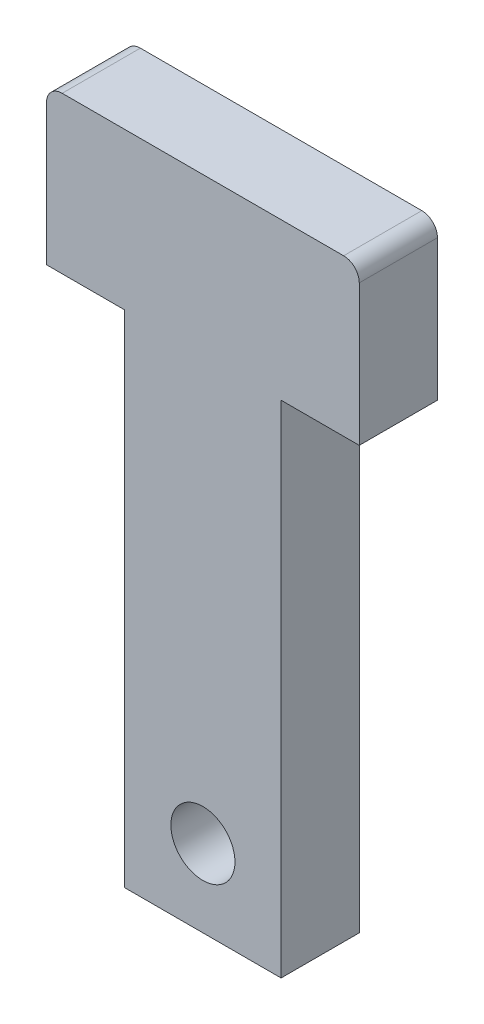
SolidWorks part; units mm, degrees
ref_plane "前基準面" through (0, 0, 0) normal (0, 0, 1) x (1, 0, 0)
ref_plane "上基準面" through (0, 0, 0) normal (0, 1, 0) x (1, 0, 0)
ref_plane "右基準面" through (0, 0, 0) normal (1, 0, 0) x (0, 0, -1)
sketch "草圖1" plane through (0, 0, 0) normal (0, 0, 1) x (1, 0, 0)
  line L0 (-5, -4.5) -> (-10, -4.5)
  line L1 (9, 5.5) -> (-9, 5.5)
  line L2 (10, 4.5) -> (10, -4.5)
  line L3 (10, -4.5) -> (5, -4.5)
  line L4 (-10, 4.5) -> (-10, -4.5)
  line L5 (0, -4.801) -> (0, 5.5) construction
  line L6 (10, 0) -> (-10, 0) construction
  line L7 (5, -36.5) -> (-5, -36.5)
  line L8 (5, -36.5) -> (5, -4.5)
  line L10 (-5, -36.5) -> (-5, -4.5)
  line L11 (0, -4.801) -> (0, -36.5) construction
  line L14 (-5, -4.5) -> (5, -4.5) construction
  line L15 (-5, -4.5) -> (-5, -9.5) construction
  line L16 (-5, -9.5) -> (5, -9.5) construction
  line L17 (5, -4.5) -> (5, -9.5) construction
  circle A0 centre (0, -31.55) radius 2.05
  arc A1 (9, 5.5) -> (10, 4.5) centre (9, 4.5) cw
  arc A2 (-9, 5.5) -> (-10, 4.5) centre (-9, 4.5) ccw
  point P0 (0, 0)
  point P4 (0, -17.2944)
  point P14 (0, -29.5)
  point P19 (10, 5.5)
  point P22 (-10, 5.5)
  dimension "D5" = 4.1
  dimension "D7" = 1
  dimension "D1" = 10
  dimension "D2" = 20
  dimension "D3" = 10
  dimension "D4" = 20
  dimension "D6" = 27
  dimension "D8" = 5
extrude "填料-伸長1" add sketch "草圖1" along normal blind 5
